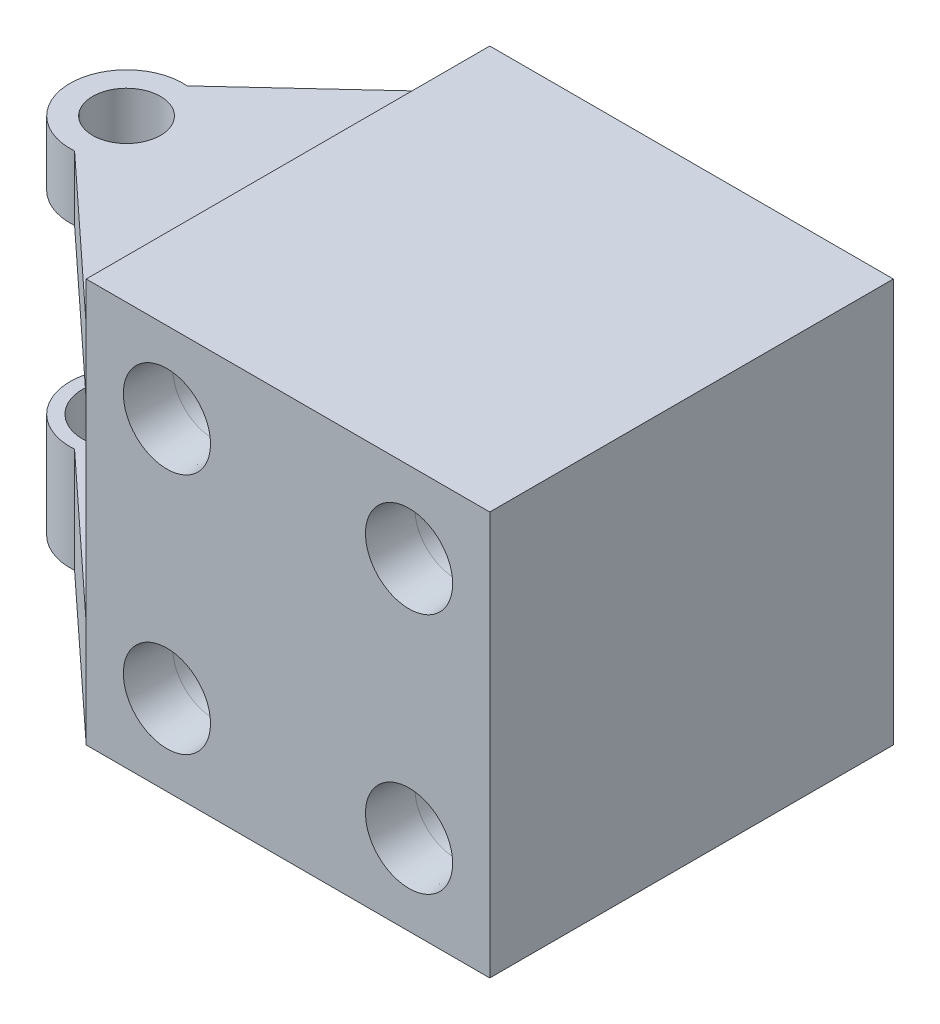
SolidWorks part; units mm, degrees
ref_plane "Front Plane" through (0, 0, 0) normal (0, 0, 1) x (1, 0, 0)
ref_plane "Top Plane" through (0, 0, 0) normal (0, 1, 0) x (1, 0, 0)
ref_plane "Right Plane" through (0, 0, 0) normal (1, 0, 0) x (0, 0, -1)
sketch "Sketch1" plane through (0, 0, 0) normal (0, 0, 1) x (1, 0, 0)
  line L1 (-12.5, 12.5) -> (12.5, 12.5)
  line L2 (-12.5, 12.5) -> (-12.5, -12.5)
  line L3 (-12.5, -12.5) -> (12.5, -12.5)
  line L4 (12.5, 12.5) -> (12.5, -12.5)
  line L5 (-12.5, 12.5) -> (12.5, -12.5) construction
  line L6 (-12.5, -12.5) -> (12.5, 12.5) construction
  point P0 (0, 0)
  dimension "D1" = 25
  dimension "D2" = 25
extrude "Boss-Extrude1" add sketch "Sketch1" along normal blind 12.5 and the other way blind 12.5
hole_wizard "CSK for M3 Oval Head Machine Screw1" positions "Sketch2" profile "Sketch3" countersink size "M3" standard "ANSI Metric"
sketch "Sketch2" plane through (0, 0, 12.5) normal (0, 0, 1) x (1, 0, 0)
  line L0 (12.5, 12.5) -> (-12.5, 12.5) construction
  line L1 (-12.5, 12.5) -> (-12.5, -12.5) construction
  point P0 (-7.5, 7.5)
  dimension "D1" = 5
  dimension "D2" = 5
sketch "Sketch3" plane through (-7.5, 7.5, 12.5) normal (1, 0, 0) x (0, -1, 0)
  line L0 (0, 0) -> (0, 11.5022)
  line L1 (0, 11.5022) -> (2.5, 10)
  line L2 (2.5, 10) -> (2.5, 2.8601)
  line L3 (2.5, 2.8601) -> (2.7, 0)
  line L5 (2.7, 0) -> (0, 0)
  line L6 (-2.5, 2.8601) -> (-2.7, 0) construction
  line L10 (0, 11.5022) -> (-2.5, 10) construction
  line L11 (0, -6.35) -> (0, 107.95) construction
  dimension "Hole Dia." = 5
  dimension "Hole Depth" = 10
  dimension "Near C'Sink Dia." = 5.4
  dimension "Near C'Sink Angle" = 8
  dimension "Drill Angle" = 118
pattern_linear "LPattern1" count 2 spacing 15 along (0, -1, 0) count 2 spacing 15 along (1, 0, 0) of "CSK for M3 Oval Head Machine Screw1"
sketch "Sketch4" plane through (0, 0, 0) normal (0, 1, 0) x (1, 0, 0)
  line L0 (-12.5, 12.5) -> (-12.5, -12.5) construction
  line L1 (-26, 0) -> (-12.5, -12.5)
  line L2 (-13.75, 0) -> (13.75, 0) construction
  line L3 (-26, 0) -> (-12.5, 12.5)
  line L4 (-12.5, 12.5) -> (-12.5, -12.5)
  circle A0 centre (-22.5, 0) radius 3.5
  circle A1 centre (-22.5, 0) radius 2.1
  dimension "D1" = 7
  dimension "D2" = 4.2
  dimension "D3" = 10
extrude "Boss-Extrude3" add sketch "Sketch4" along normal blind 4 from offset 6 contours A0 L1 L4 L3 | A1 L1 A0 L3 | A1 L3 A0 | A1 L1 A0 | A1 L3 L1 region at (-24.0484, 0, -1.6723) region at (-24.4251, 0, -2.0792) region at (-24.4251, 0, 2.0792) region at (-15.8969, 0, 0)
extrude "Boss-Extrude5" add sketch "Sketch4<5>" against normal up to surface (12.5 mm away) from offset 6 contours L3 A0 | L1 A0 L3 A1 | L1 A0 | A1 | A0 L1 L4 L3 region at (-24.0484, 0, -1.6723) region at (-24.4251, 0, -2.0792) region at (-24.4251, 0, 2.0792) region at (-15.8969, 0, 0) region at (-22.5, 0, 0) up to face at (0, -12.5, 0) offset against normal yes
sketch "Sketch4<5>" plane through (0, 0, 0) normal (0, 1, 0) x (1, 0, 0) same geometry as "Sketch4"
hole_wizard "CSK for M3 Oval Head Machine Screw3" positions "Sketch7" profile "Sketch8" countersink size "M3" standard "ANSI Metric"
sketch "Sketch7" plane through (0, -6, 0) normal (0, 1, 0) x (1, 0, 0)
  line L0 (-12.5, 12.5) -> (-12.5, -12.5) construction
  point P0 (-22.5, 0)
  dimension "D1" = 10
  dimension "D2" = 12.5
sketch "Sketch8" plane through (-22.5, -6, 0) normal (1, 0, 0) x (0, 0, 1)
  line L0 (0, 0) -> (0, 11.5022)
  line L1 (0, 11.5022) -> (2.5, 10)
  line L2 (2.5, 10) -> (2.5, 2.8601)
  line L3 (2.5, 2.8601) -> (2.7, 0)
  line L5 (2.7, 0) -> (0, 0)
  line L6 (-2.5, 2.8601) -> (-2.7, 0) construction
  line L10 (0, 11.5022) -> (-2.5, 10) construction
  line L11 (0, -6.35) -> (0, 107.95) construction
  dimension "Hole Dia." = 5
  dimension "Hole Depth" = 10
  dimension "Near C'Sink Dia." = 5.4
  dimension "Near C'Sink Angle" = 8
  dimension "Drill Angle" = 118
